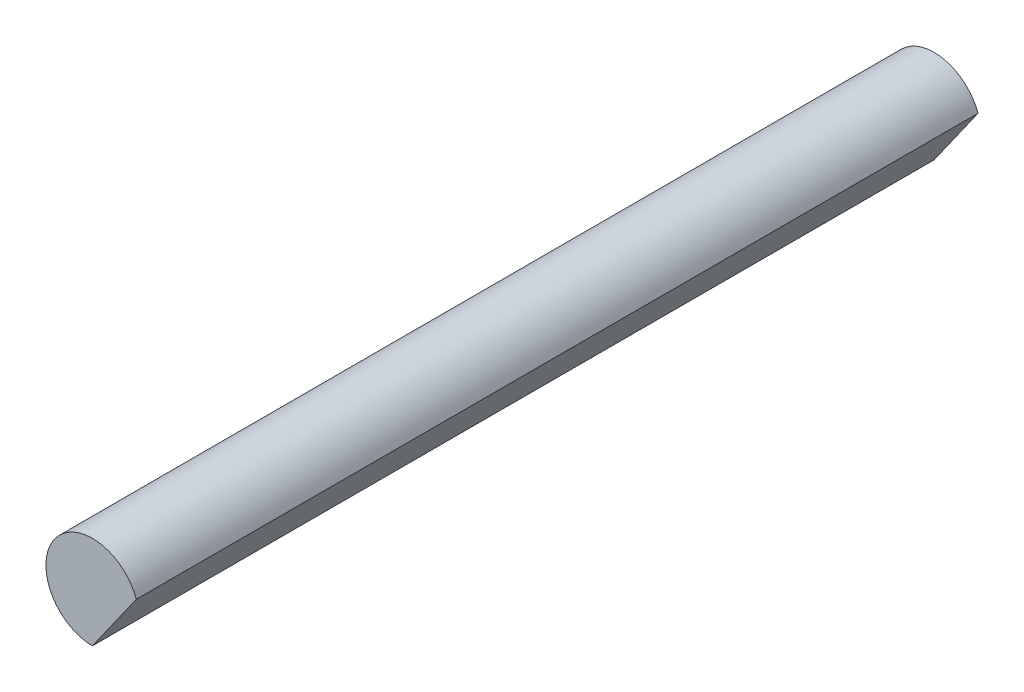
SolidWorks part; units mm, degrees
material "1060 Alloy"
ref_plane "Front Plane" through (0, 0, 0) normal (0, 0, 1) x (1, 0, 0)
ref_plane "Top Plane" through (0, 0, 0) normal (0, 1, 0) x (1, 0, 0)
ref_plane "Right Plane" through (0, 0, 0) normal (1, 0, 0) x (0, 0, -1)
sketch "Sketch1" plane through (0, 0, 0) normal (0, 0, 1) x (1, 0, 0)
  line L2 (-0.0017, -1.5) -> (1.4119, 0.5065)
  arc A2 (1.4119, 0.5065) -> (-0.0017, -1.5) centre (0, 0) ccw
extrude "Boss-Extrude1" add sketch "Sketch1" along normal up to surface (27.12 mm away)
